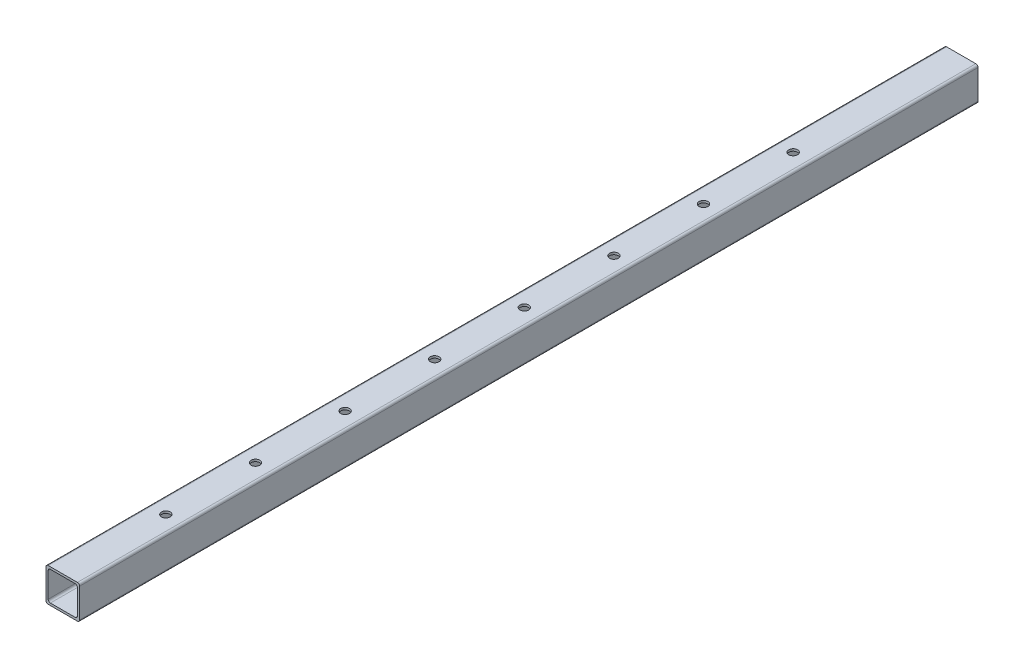
SolidWorks part; units mm, degrees
ref_plane "Front Plane" through (0, 0, 0) normal (0, 0, 1) x (1, 0, 0)
ref_plane "Top Plane" through (0, 0, 0) normal (0, 1, 0) x (1, 0, 0)
ref_plane "Right Plane" through (0, 0, 0) normal (1, 0, 0) x (0, 0, -1)
sketch "Sketch1" plane through (0, 0, 0) normal (0, 0, 1) x (1, 0, 0)
  line L0 (-9.525, 0) -> (9.525, 0) construction
  line L1 (0, -9.525) -> (0, 9.525) construction
  line L2 (8.2804, 0) -> (8.2804, 8.2804) construction
  line L3 (-9.525, -9.525) -> (9.525, -9.525) construction
  line L4 (-9.525, -9.525) -> (-9.525, 9.525) construction
  line L5 (-9.525, 9.525) -> (9.525, 9.525) construction
  line L6 (9.525, -9.525) -> (9.525, 9.525) construction
  line L7 (-9.525, -9.525) -> (9.525, 9.525) construction
  line L8 (-9.525, 9.525) -> (9.525, -9.525) construction
  line L9 (8.2804, 8.2804) -> (-8.2804, 8.2804) construction
  line L10 (-8.2804, 8.2804) -> (-8.2804, -8.2804) construction
  line L11 (-8.2804, -8.2804) -> (8.2804, -8.2804) construction
  line L12 (8.2804, -8.2804) -> (8.2804, 0) construction
  point P0 (0, 0)
  point P4 (0, 0)
  point P9 (0, 0)
  point P10 (8.2804, 0)
  point P13 (0, -8.2804)
  point P14 (-8.2804, 0)
  point P15 (0, 8.2804)
  dimension "Width" = 19.05
  dimension "Wall Thickness" = 1.2446
  dimension "Height" = 19.05
  dimension "D1" = 1.2446
  dimension "D2" = 1.2446
  dimension "D3" = 1.2446
sketch "Sketch2" plane through (0, 0, 0) normal (1, 0, 0) x (0, 0, -1)
  line L0 (254.635, 9.525) -> (-254.635, 9.525) construction
  point P3 (-232.7275, 9.525)
  point P5 (232.7275, 9.525)
  point P7 (0, 9.525)
  dimension "D1" = 21.9075
  dimension "D2" = 21.9075
  dimension "Length" = 509.27
sketch "Sketch3" plane through (0, 0, 0) normal (0, 0, 1) x (1, 0, 0)
  line L1 (9.525, 9.525) -> (-9.525, 9.525)
  line L2 (-9.525, 9.525) -> (-9.525, -9.525)
  line L3 (-9.525, -9.525) -> (9.525, -9.525) construction
  line L4 (-9.525, -9.525) -> (9.525, -9.525)
  line L5 (9.525, -9.525) -> (9.525, 9.525)
  line L6 (-8.2804, 8.2804) -> (8.2804, 8.2804)
  line L7 (8.2804, 8.2804) -> (8.2804, -8.2804)
  line L8 (8.2804, -8.2804) -> (-8.2804, -8.2804)
  line L9 (-8.2804, -8.2804) -> (-8.2804, 8.2804)
extrude "Boss-Extrude1" add sketch "Sketch3" along normal mid plane 509.27
fillet "Fillet1" radius 1.2446 8 edges at (-9.525, 9.525, 0) (8.2804, -8.2804, 0) (-8.2804, -8.2804, 0) (-8.2804, 8.2804, 0) (8.2804, 8.2804, 0) (9.525, -9.525, 0) (-9.525, -9.525, 0) (9.525, 9.525, 0)
sketch "Sketch4" plane through (0, 9.525, 0) normal (0, 1, 0) x (1, 0, 0)
  line L0 (0, 254.635) -> (0, 159.385) construction
  line L1 (8.2804, 254.635) -> (-8.2804, 254.635) construction
  line L2 (0, 159.385) -> (0, 108.585) construction
  circle A0 centre (0, 159.385) radius 2.4892
  circle A1 centre (0, 108.585) radius 2.4892
  circle A2 centre (0, 57.785) radius 2.4892
  circle A3 centre (0, 6.985) radius 2.4892
  circle A4 centre (0, -43.815) radius 2.4892
  circle A5 centre (0, -94.615) radius 2.4892
  circle A6 centre (0, -145.415) radius 2.4892
  circle A7 centre (0, -196.215) radius 2.4892
  dimension "D2" = 4.9784
  dimension "D4" = 4.9784
  dimension "D1" = 95.25
  dimension "D3" = 50.8
  dimension "D5" = 7
extrude "Cut-Extrude1" cut sketch "Sketch4" against normal through all
sketch "Sketch6" plane through (-9.525, 0, 0) normal (-1, 0, 0) x (0, 0, 1)
  line L0 (-254.635, 0) -> (-179.705, 0) construction
  line L1 (-254.635, 8.2804) -> (-254.635, -8.2804) construction
  line L2 (-182.118, -1.651) -> (-187.198, -1.651)
  line L7 (-182.118, -6.477) -> (-177.292, -1.651) construction
  line L12 (-177.292, -6.477) -> (-182.118, -6.477)
  line L13 (-177.292, -6.477) -> (-177.292, -1.651)
  line L14 (-177.292, -1.651) -> (-182.118, -1.651)
  line L15 (-182.118, -6.477) -> (-182.118, -1.651) construction
  line L16 (-192.278, 9.525) -> (-192.278, -6.477)
  line L17 (-177.292, -6.477) -> (-182.118, -1.651) construction
  line L18 (-254.635, 9.525) -> (254.635, 9.525) construction
  line L19 (-192.278, -6.477) -> (-182.118, -6.477)
  line L20 (-187.198, -1.651) -> (-187.198, 9.525)
  line L21 (-187.198, 9.525) -> (-192.278, 9.525)
  point P12 (-179.705, -4.064)
  dimension "D1" = 74.93
  dimension "D2" = 16.002
  dimension "D3" = 4.826
  dimension "D4" = 4.826
  dimension "D5" = 10.16
  dimension "D6" = 5.08
extrude "Cut-Extrude3" [suppressed] cut sketch "Sketch6" along normal blind 6.35 from surface starting at face at (9.525, 0, 0)
pattern_linear "LPattern2" [suppressed] count 8 spacing 50.8 of bodies 108
equation "\"D1@Boss-Extrude1\" = \"Length@Sketch2\""
equation "\"D1@Sketch2\" = \"Width@Sketch1\" * 1.15"
equation "\"D2@Sketch2\"=\"D1@Sketch2\""
equation "\"D1@Sketch1\"=\"Wall Thickness@Sketch1\""
equation "\"D2@Sketch1\"=\"Wall Thickness@Sketch1\""
equation "\"D3@Sketch1\"=\"Wall Thickness@Sketch1\""
equation "\"D1@Fillet1\"=\"Wall Thickness@Sketch1\""
